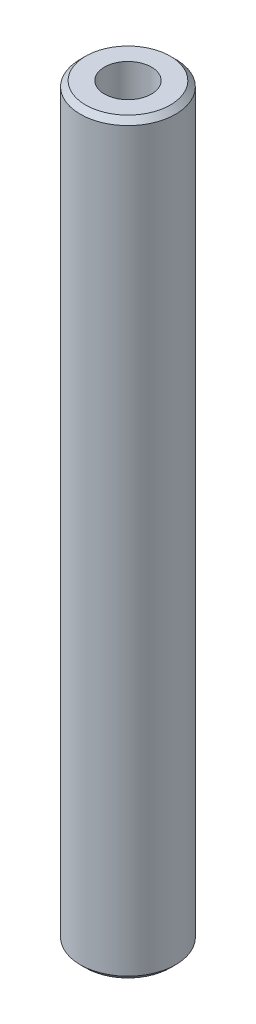
SolidWorks part; units mm, degrees
ref_plane "Front Plane" through (0, 0, 0) normal (0, 0, 1) x (1, 0, 0)
ref_plane "Top Plane" through (0, 0, 0) normal (0, 1, 0) x (1, 0, 0)
ref_plane "Right Plane" through (0, 0, 0) normal (1, 0, 0) x (0, 0, -1)
sketch "Sketch1" plane through (0, 0, 0) normal (0, 1, 0) x (1, 0, 0)
  circle A0 centre (0, 0) radius 15
  dimension "SHAFT_OD" = 30
extrude "Boss-Extrude1" add sketch "Sketch1" along normal blind 235.1549
sketch "Sketch2" plane through (0, 0, 0) normal (0, 1, 0) x (1, 0, 0)
  circle A0 centre (0, 0) radius 7.3792
  dimension "BORE_D" = 14.7585
extrude "Cut-Extrude1" cut sketch "Sketch2" along normal through all
chamfer "Chamfer1" distance 1.6753 angle 45 2 edges at (0, 235.1549, 15) (0, 0, 15)
